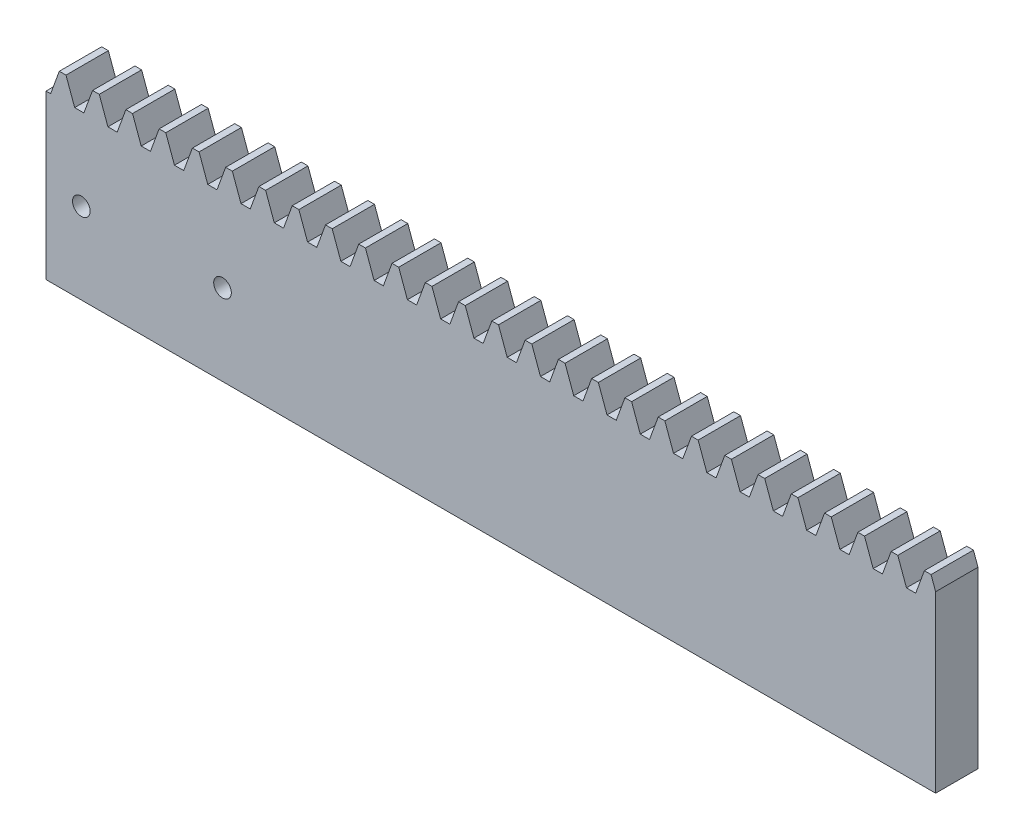
SolidWorks part; units mm, degrees
extrude "Blank" add sketch "BlankSke" against normal blind 6
sketch "BlankSke" plane through (0, 0, 0) normal (0, 0, 1) x (1, 0, 0)
  line L1 (0, 0) -> (126, 0)
  line L2 (0, 0) -> (0, 26.5)
  line L3 (0, 26.5) -> (126, 26.5)
  line L4 (126, 0) -> (126, 26.5)
  dimension "Length" = 126
ref_plane "Plane1" through (0, 0, 0) normal (0, 0, 1) x (1, 0, 0)
ref_plane "Plane2" through (0, 0, 0) normal (0, 1, 0) x (1, 0, 0)
ref_plane "Plane3" through (0, 0, 0) normal (1, 0, 0) x (0, 0, -1)
sketch "HoldingSke" plane through (0, 0, 0) normal (0, 1, 0) x (1, 0, 0)
  line L0 (0, 0) -> (0.0928, 0.6602)
  line L1 (-15, 0) -> (100, 0) construction
  line L2 (0, 0) -> (-2.1039, 2.3779)
  line L3 (0, 0) -> (-11.863, 4.5341)
  line L4 (0, 0) -> (7.2428, 4.7035)
  line L5 (0, 0) -> (-23.7986, -8.8762)
  line L6 (0, 0) -> (-10.5278, -7.1032)
  line L9 (-71.009, 38.7566) -> (69.9449, 90.0596)
  line L10 (-76.2, 3.8779) -> (-51.2, 3.8779)
  line L11 (0, 0) -> (-6, 0)
  line L12 (-76.2, 101.6) -> (-76.147, 101.6)
  line L13 (24.9733, 27.94) -> (52.9518, 28.4284)
  line L14 (24.9733, 27.94) -> (24.9743, 27.94)
  line L15 (24.9733, 27.94) -> (100.4006, 29.5858)
  circle A0 centre (0, 0) radius 19.05
  circle A1 centre (0, 0) radius 12.5
  circle A2 centre (0, 0) radius 12.7
  dimension "Num_teeth" = 33
  dimension "Width" = 6
  dimension "Pitch_height" = 25
sketch "TooCutSkeIll" plane through (0, 0, 0) normal (0, 0, 1) x (1, 0, 0)
  line L0 (-1.8687, 26.4605) -> (-0.7447, 23.3724)
  line L1 (-0.3914, 23.125) -> (0.3914, 23.125)
  line L2 (0.7447, 23.3724) -> (1.8687, 26.4605)
  line L3 (126, 26.5) -> (0, 26.5) construction
  line L4 (0, 0) -> (0, 64.897) construction
  line L5 (-13.208, 25) -> (12.954, 25) construction
  line L6 (0, 0) -> (126, 0) construction
  line L7 (1.3371, 25) -> (1.3371, 48.7463) construction
  line L8 (-1.3371, 25) -> (-1.3371, 48.7463) construction
  line L9 (1.9251, 26.5) -> (1.9251, 26.5254)
  line L10 (-1.9251, 26.5) -> (-1.9251, 26.5254)
  line L11 (-1.9251, 26.5254) -> (1.9251, 26.5254)
  arc A0 (0.3914, 23.125) -> (0.7447, 23.3724) centre (0.3914, 23.501) ccw
  arc A1 (-0.7447, 23.3724) -> (-0.3914, 23.125) centre (-0.3914, 23.501) ccw
  arc A2 (1.9251, 26.5) -> (1.8687, 26.4605) centre (1.9251, 26.44) ccw
  arc A3 (-1.8687, 26.4605) -> (-1.9251, 26.5) centre (-1.9251, 26.44) ccw
  dimension "Addendum_plus" = 1.5254
  dimension "Pitch_height" = 25
  dimension "Pressure_angle" = 20
  dimension "Gap_width" = 2.6742
  dimension "Dedendum" = 1.875
extrude "ToothCutIll" [suppressed] cut sketch "TooCutSkeIll" against normal through all
sketch "TooCutSkeSim" plane through (0, 0, 0) normal (0, 0, 1) x (1, 0, 0)
  line L0 (0.6547, 23.125) -> (-0.6547, 23.125)
  line L1 (1.8923, 26.5254) -> (0.6547, 23.125)
  line L2 (0, 17.4625) -> (0, 53.467) construction
  line L3 (1.8923, 26.5254) -> (-1.8923, 26.5254)
  line L6 (-1.8923, 26.5254) -> (-0.6547, 23.125)
  line L9 (-1.3371, 25) -> (1.3371, 25) construction
  line L10 (0, 0) -> (126, 0) construction
  line L11 (1.3371, 25) -> (1.3371, 53.467) construction
  line L12 (-1.3371, 25) -> (-1.3371, 53.467) construction
  dimension "Addendum_plus" = 1.5254
  dimension "Pitch_height" = 25
  dimension "Pressure_angle" = 20
  dimension "Gap_width" = 2.6742
  dimension "Dedendum" = 1.875
extrude "ToothCutSim" cut sketch "TooCutSkeSim" against normal through all
pattern_linear "TeethCuts" count 33 spacing 4.7124 along (1, 0, 0) of "ToothCutIll", "ToothCutSim"
sketch "Esquisse1" plane through (0, 0, 0) normal (0, 0, 1) x (1, 0, 0)
  line L0 (0, 23.125) -> (0, 0) construction
  line L1 (0, 0) -> (126, 0) construction
  circle A0 centre (5, 11.5) radius 1.25
  circle A1 centre (25, 11.5) radius 1.25
  dimension "D1" = 2.5
  dimension "D2" = 2.5
  dimension "D3" = 5
  dimension "D4" = 20
  dimension "D5" = 11.5
extrude "Enlèv. mat.-Extru.1" cut sketch "Esquisse1" against normal blind 6
equation "' \"Module@HoldingSke\" = 6.35"
equation "' \"Num_teeth@HoldingSke\" = 12"
equation "' \"Ap@HoldingSke\" =  20"
equation "' \"Ap@HoldingSke\" = 20"
equation "' \"Width@HoldingSke\" = 0.25 * 25.4"
equation "' \"Show_teeth@HoldingSke\" = 500"
equation "' \"Backlash@HoldingSke\" = 0.009 * 25.4"
equation "' \"Addendum_fac@HoldingSke\" = 1.0"
equation "' \"Dedendum_fac@HoldingSke\" = 1.25"
equation "' \"Dedendum_add@HoldingSke\" = 0.00005 * 25.4"
equation "' \"Clearance_fac@HoldingSke\" = 0.25"
equation "' \"Pitch_height@HoldingSke\" = 1 * 25.4"
equation "' \"Length@HoldingSke\" = 4.71 * 25.4"
equation "\"Pitch@HoldingSke\" = 1 / \"Module@HoldingSke\""
equation "\"MPH@HoldingSke\" = \"Dedendum_fac@HoldingSke\" / \"Pitch@HoldingSke\" + 2 * \"Dedendum_add@HoldingSke\" + 0.002 * 25.4"
equation "\"MPH@HoldingSke\" = ((sgn( \"MPH@HoldingSke\" - \"Pitch_height@HoldingSke\")+1)*( \"MPH@HoldingSke\" - \"Pitch_height@HoldingSke\"))/2 + \"Pitch_height@HoldingSke\""
equation "\"Blank_height@BlankSke\" = \"Pitch_height@HoldingSke\" + \"Addendum_fac@HoldingSke\"  / \"Pitch@HoldingSke\" "
equation "\"Face_width@Blank\" = \"Width@HoldingSke\""
equation "\"Pressure_angle@TooCutSkeIll\" = \"Ap@HoldingSke\""
equation "\"Addendum_plus@TooCutSkeIll\" =  \"Addendum_fac@HoldingSke\"  / \"Pitch@HoldingSke\" + 0.001 *25.4"
equation "\"Dedendum@TooCutSkeIll\" = \"Dedendum_fac@HoldingSke\"  / \"Pitch@HoldingSke\""
equation "\"Pitch_height@TooCutSkeIll\" =  \"MPH@HoldingSke\""
equation "\"Gap_width@TooCutSkeIll\" = 3.14159265 / 2 / \"Pitch@HoldingSke\" + 6 * \"Backlash@HoldingSke\""
equation "\"Pressure_angle@TooCutSkeSim\" = \"Ap@HoldingSke\""
equation "\"Addendum_plus@TooCutSkeSim\" =  \"Addendum_fac@HoldingSke\"  / \"Pitch@HoldingSke\" + 0.001 * 25.4"
equation "\"Dedendum@TooCutSkeSim\" = \"Dedendum_fac@HoldingSke\"  / \"Pitch@HoldingSke\""
equation "\"Pitch_height@TooCutSkeSim\" =  \"MPH@HoldingSke\""
equation "\"Gap_width@TooCutSkeSim\" = 3.14159265 / 2 / \"Pitch@HoldingSke\" + 6 * \"Backlash@HoldingSke\""
equation "\"Root_fillet@TooCutSkeIll\" = \"Clearance_fac@HoldingSke\" / \"Pitch@HoldingSke\" + \"Dedendum_add@HoldingSke\""
equation "\"Break_rad@TooCutSkeIll\" = 0.02 / \"Pitch@HoldingSke\" * 2"
equation "\"Linear_pitch@TeethCuts\" = 3.14159265 / \"Pitch@HoldingSke\""
equation "\"Num_teeth@HoldingSke\" = int( ( \"Length@HoldingSke\" + 0 ) / (3.14159265 / \"Pitch@HoldingSke\")) + 0.9999  + 1"
equation " \"Num_teeth@TeethCuts\" = int( \"Show_teeth@HoldingSke\" ) + 1"
equation " \"Num_teeth@TeethCuts\" = ((sgn( \"Num_teeth@TeethCuts\" - \"Num_teeth@HoldingSke\" )-1)*( \"Num_teeth@TeethCuts\" - \"Num_teeth@HoldingSke\" ))/-2+ \"Num_teeth@HoldingSke\""
equation " \"Num_teeth@TeethCuts\" = ((sgn( \"Num_teeth@TeethCuts\" - 2.0)+1)*( \"Num_teeth@TeethCuts\" - 2.0))/2 +2.0"
